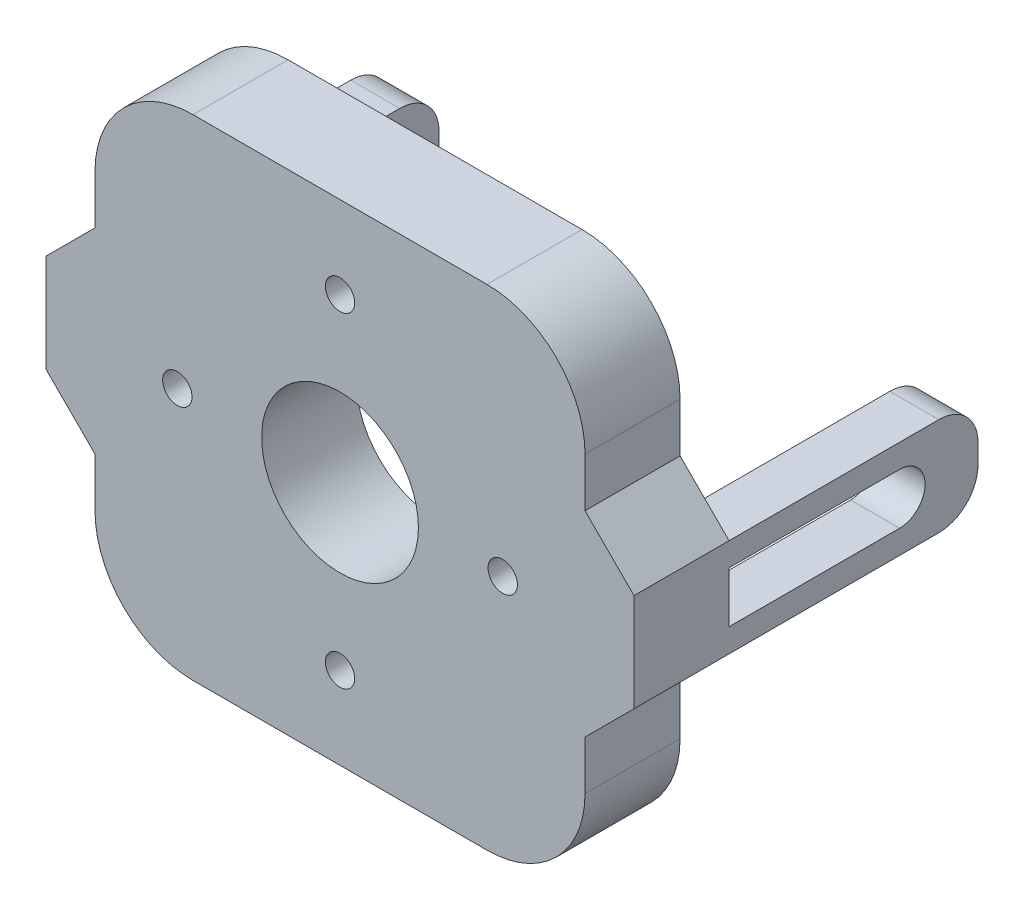
SolidWorks part; units mm, degrees
ref_plane "Front Plane" through (0, 0, 0) normal (0, 0, 1) x (1, 0, 0)
ref_plane "Top Plane" through (0, 0, 0) normal (0, 1, 0) x (1, 0, 0)
ref_plane "Right Plane" through (0, 0, 0) normal (1, 0, 0) x (0, 0, -1)
sketch "Sketch1" plane through (0, 0, 0) normal (0, 0, 1) x (1, 0, 0)
  line L0 (0, 0) -> (18.1, 0)
  line L1 (-25, -25) -> (25, -25)
  line L2 (-25, -25) -> (-25, 25)
  line L3 (-25, 25) -> (25, 25)
  line L4 (25, -25) -> (25, 25)
  line L5 (-25, -25) -> (25, 25) construction
  line L6 (-25, 25) -> (25, -25) construction
  circle A0 centre (0, 0) radius 8
  circle A1 centre (16.6, 0) radius 1.5
  circle A2 centre (0, -16.6) radius 1.5
  circle A3 centre (-16.6, 0) radius 1.5
  circle A4 centre (0, 16.6) radius 1.5
  point P19 (0, 0)
  dimension "D1" = 16
  dimension "D3" = 3
  dimension "D2" = 50
  dimension "D4" = 18.1
  dimension "D5" = 4
extrude "Boss-Extrude1" add sketch "Sketch1" along normal blind 9.7
sketch "Sketch2" plane through (0, 0, 9.7) normal (0, 0, 1) x (1, 0, 0)
  line L0 (-19.725, 0) -> (-13.475, 0)
  line L1 (-16.6, -3) -> (-16.6, 3)
  line L2 (-19.725, -1.2266) -> (-19.725, 1.2266) construction
  line L4 (-18.5752, 0) -> (-20.8748, 0) construction
  line L5 (-19.2248, 2.093) -> (-17.1002, 3.3196) construction
  line L6 (-17.5876, 1.7106) -> (-18.7374, 3.7021) construction
  line L7 (-16.0998, 3.3196) -> (-13.9752, 2.093) construction
  line L8 (-15.6124, 1.7106) -> (-14.4626, 3.7021) construction
  line L9 (-13.475, 1.2266) -> (-13.475, -1.2266) construction
  line L10 (-14.6248, 0) -> (-12.3252, 0) construction
  line L11 (-13.9752, -2.093) -> (-16.0998, -3.3196) construction
  line L12 (-15.6124, -1.7106) -> (-14.4626, -3.7021) construction
  line L13 (-17.1002, -3.3196) -> (-19.2248, -2.093) construction
  line L14 (-17.5876, -1.7106) -> (-18.7374, -3.7021) construction
  line L15 (-19.725, 0) -> (-18.1625, -2.7063)
  line L17 (-18.1625, -2.7063) -> (-15.0375, -2.7063)
  line L18 (-15.0375, -2.7063) -> (-13.475, 0)
  line L20 (-13.475, 0) -> (-15.0375, 2.7063)
  line L22 (-15.0375, 2.7063) -> (-18.1625, 2.7063)
  line L23 (-18.1625, 2.7063) -> (-19.725, 0)
  line L26 (-2.6111, 14.9422) -> (0.0953, 13.3797)
  line L27 (0.0953, 19.6297) -> (0.0953, 13.3797)
  line L28 (0.0953, 19.6297) -> (-2.6111, 18.0672)
  line L29 (-2.6111, 18.0672) -> (-2.6111, 14.9422)
  line L30 (2.8016, 14.9422) -> (2.8016, 18.0672)
  line L31 (0.0953, 13.3797) -> (2.8016, 14.9422)
  line L32 (2.8016, 18.0672) -> (0.0953, 19.6297)
  line L33 (15.0375, 2.5158) -> (13.475, -0.1905)
  line L34 (19.725, -0.1905) -> (13.475, -0.1905)
  line L35 (19.725, -0.1905) -> (18.1625, 2.5158)
  line L36 (18.1625, 2.5158) -> (15.0375, 2.5158)
  line L37 (15.0375, -2.8969) -> (18.1625, -2.8969)
  line L38 (13.475, -0.1905) -> (15.0375, -2.8969)
  line L39 (18.1625, -2.8969) -> (19.725, -0.1905)
  line L40 (2.6111, -15.1328) -> (-0.0953, -13.5703)
  line L41 (-0.0953, -19.8203) -> (-0.0953, -13.5703)
  line L42 (-0.0953, -19.8203) -> (2.6111, -18.2578)
  line L43 (2.6111, -18.2578) -> (2.6111, -15.1328)
  line L44 (-2.8016, -15.1328) -> (-2.8016, -18.2578)
  line L45 (-0.0953, -13.5703) -> (-2.8016, -15.1328)
  line L46 (-2.8016, -18.2578) -> (-0.0953, -19.8203)
  circle A2 centre (-16.6, 0) radius 1.5 construction
  circle A3 centre (-16.6, 0) radius 1.5
  circle A4 centre (-16.6, 0) radius 3.125 construction
  point P5 (-16.6, 0)
  point P8 (-16.6, 0)
  point P25 (-19.725, 0)
  point P63 (-19.725, 0)
  point P143 (0, -0.0953)
  dimension "D3" = 6.25
  dimension "D1" = 5.4127
  dimension "D4" = 6
  dimension "D5" = 4
sketch "Sketch6" plane through (0, 0, 9.7) normal (0, 0, 1) x (1, 0, 0)
  line L0 (-18.1625, -2.7063) -> (-15.0375, -2.7063) construction
  line L1 (-19.725, 0) -> (-18.1625, -2.7063) construction
  line L2 (-18.1625, 2.7063) -> (-19.725, 0) construction
  line L3 (-15.0375, 2.7063) -> (-18.1625, 2.7063) construction
  line L4 (-13.475, 0) -> (-15.0375, 2.7063) construction
  line L5 (-15.0375, -2.7063) -> (-13.475, 0) construction
  line L6 (2.6111, -18.2578) -> (2.6111, -15.1328) construction
  line L7 (-0.0953, -19.8203) -> (-0.0953, -13.5703) construction
  line L8 (-0.0953, -19.8203) -> (2.6111, -18.2578) construction
  line L9 (-2.8016, -18.2578) -> (-0.0953, -19.8203) construction
  line L10 (-2.8016, -15.1328) -> (-2.8016, -18.2578) construction
  line L11 (-0.0953, -13.5703) -> (-2.8016, -15.1328) construction
  line L12 (2.6111, -15.1328) -> (-0.0953, -13.5703) construction
  line L13 (15.0375, -2.8969) -> (18.1625, -2.8969) construction
  line L14 (19.725, -0.1905) -> (13.475, -0.1905) construction
  line L15 (18.1625, -2.8969) -> (19.725, -0.1905) construction
  line L16 (19.725, -0.1905) -> (18.1625, 2.5158) construction
  line L17 (18.1625, 2.5158) -> (15.0375, 2.5158) construction
  line L18 (15.0375, 2.5158) -> (13.475, -0.1905) construction
  line L19 (13.475, -0.1905) -> (15.0375, -2.8969) construction
  line L20 (0.0953, 19.6297) -> (-2.6111, 18.0672) construction
  line L21 (-2.6111, 18.0672) -> (-2.6111, 14.9422) construction
  line L22 (2.8016, 18.0672) -> (0.0953, 19.6297) construction
  line L23 (0.0953, 19.6297) -> (0.0953, 13.3797) construction
  line L24 (2.8016, 14.9422) -> (2.8016, 18.0672) construction
  line L25 (0.0953, 13.3797) -> (2.8016, 14.9422) construction
  line L26 (-2.6111, 14.9422) -> (0.0953, 13.3797) construction
  line L27 (-18.1625, -2.7063) -> (-15.0375, -2.7063)
  line L28 (-19.725, 0) -> (-18.1625, -2.7063)
  line L29 (-18.1625, 2.7063) -> (-19.725, 0)
  line L30 (-15.0375, 2.7063) -> (-18.1625, 2.7063)
  line L31 (-13.475, 0) -> (-15.0375, 2.7063)
  line L32 (-15.0375, -2.7063) -> (-13.475, 0)
  line L33 (2.6111, -18.2578) -> (2.6111, -15.1328)
  line L34 (-0.0953, -19.8203) -> (-0.0953, -13.5703)
  line L35 (-0.0953, -19.8203) -> (2.6111, -18.2578)
  line L36 (-2.8016, -18.2578) -> (-0.0953, -19.8203)
  line L37 (-2.8016, -15.1328) -> (-2.8016, -18.2578)
  line L38 (-0.0953, -13.5703) -> (-2.8016, -15.1328)
  line L39 (2.6111, -15.1328) -> (-0.0953, -13.5703)
  line L40 (15.0375, -2.8969) -> (18.1625, -2.8969)
  line L41 (19.725, -0.1905) -> (13.475, -0.1905)
  line L42 (18.1625, -2.8969) -> (19.725, -0.1905)
  line L43 (19.725, -0.1905) -> (18.1625, 2.5158)
  line L44 (18.1625, 2.5158) -> (15.0375, 2.5158)
  line L45 (15.0375, 2.5158) -> (13.475, -0.1905)
  line L46 (13.475, -0.1905) -> (15.0375, -2.8969)
  line L47 (0.0953, 19.6297) -> (-2.6111, 18.0672)
  line L48 (-2.6111, 18.0672) -> (-2.6111, 14.9422)
  line L49 (2.8016, 18.0672) -> (0.0953, 19.6297)
  line L50 (0.0953, 19.6297) -> (0.0953, 13.3797)
  line L51 (2.8016, 14.9422) -> (2.8016, 18.0672)
  line L52 (0.0953, 13.3797) -> (2.8016, 14.9422)
  line L53 (-2.6111, 14.9422) -> (0.0953, 13.3797)
  circle A0 centre (16.6, 0) radius 1.5 construction
  circle A1 centre (0, -16.6) radius 1.5 construction
  circle A2 centre (0, 16.6) radius 1.5 construction
  circle A3 centre (-16.6, 0) radius 1.5 construction
  circle A4 centre (16.6, 0) radius 1.5
  circle A5 centre (0, -16.6) radius 1.5
  circle A6 centre (0, 16.6) radius 1.5
  circle A7 centre (-16.6, 0) radius 1.5
  point P0 (-2.6111, 18.0672)
fillet "Fillet2" radius 10 4 edges at (-25, -25, 4.85) (25, -25, 4.85) (25, 25, 4.85) (-25, 25, 4.85)
sketch "Sketch7" plane through (25, 0, 0) normal (1, 0, 0) x (0, 0, -1)
  line L1 (-9.7, 5) -> (25.4, 5)
  line L2 (-9.7, 5) -> (-9.7, -5)
  line L3 (-9.7, -5) -> (25.4, -5)
  line L4 (25.4, 5) -> (25.4, -5)
  line L5 (0, 0) -> (20, 0) construction
  line L6 (0, -15) -> (0, 15) construction
  line L7 (17.4, 2.6) -> (0, 2.6)
  line L8 (0, 2.6) -> (0, -2.6)
  line L9 (0, -2.6) -> (17.4, -2.6)
  line L10 (-9.7, -15) -> (-9.7, 15) construction
  circle A0 centre (17.4, 0) radius 2.6
  dimension "D1" = 5.2
  dimension "D5" = 8
  dimension "D2" = 5
  dimension "D3" = 5
  dimension "D4" = 20
extrude "Boss-Extrude3" add sketch "Sketch7" along normal blind 5
pattern_circular "CirPattern6" count 2 every 180 about axis through (0, 0, 0) along (0, 0, 1) of "Boss-Extrude3"
sketch "Sketch9" plane through (0, 0, 0) normal (0, 0, -1) x (-1, 0, 0)
  line L0 (2.8016, -15.1328) -> (2.8016, -18.2578) construction
  line L1 (0.0953, -13.5703) -> (2.8016, -15.1328) construction
  line L2 (-2.6111, -15.1328) -> (0.0953, -13.5703) construction
  line L3 (-2.6111, -18.2578) -> (-2.6111, -15.1328) construction
  line L4 (0.0953, -19.8203) -> (-2.6111, -18.2578) construction
  line L5 (2.8016, -18.2578) -> (0.0953, -19.8203) construction
  line L6 (18.1625, -2.7063) -> (15.0375, -2.7063) construction
  line L7 (19.725, 0) -> (18.1625, -2.7063) construction
  line L8 (18.1625, 2.7063) -> (19.725, 0) construction
  line L9 (15.0375, 2.7063) -> (18.1625, 2.7063) construction
  line L10 (13.475, 0) -> (15.0375, 2.7063) construction
  line L11 (15.0375, -2.7063) -> (13.475, 0) construction
  line L12 (2.6111, 14.9422) -> (-0.0953, 13.3797) construction
  line L13 (2.6111, 18.0672) -> (2.6111, 14.9422) construction
  line L14 (-0.0953, 19.6297) -> (2.6111, 18.0672) construction
  line L15 (-2.8016, 18.0672) -> (-0.0953, 19.6297) construction
  line L16 (-2.8016, 14.9422) -> (-2.8016, 18.0672) construction
  line L17 (-0.0953, 13.3797) -> (-2.8016, 14.9422) construction
  line L18 (-13.475, -0.1905) -> (-15.0375, -2.8969) construction
  line L19 (-15.0375, 2.5158) -> (-13.475, -0.1905) construction
  line L20 (-18.1625, 2.5158) -> (-15.0375, 2.5158) construction
  line L21 (-19.725, -0.1905) -> (-18.1625, 2.5158) construction
  line L22 (-18.1625, -2.8969) -> (-19.725, -0.1905) construction
  line L23 (-15.0375, -2.8969) -> (-18.1625, -2.8969) construction
  line L24 (2.8016, -15.1328) -> (2.8016, -18.2578)
  line L25 (0.0953, -13.5703) -> (2.8016, -15.1328)
  line L26 (-2.6111, -15.1328) -> (0.0953, -13.5703)
  line L27 (-2.6111, -18.2578) -> (-2.6111, -15.1328)
  line L28 (0.0953, -19.8203) -> (-2.6111, -18.2578)
  line L29 (2.8016, -18.2578) -> (0.0953, -19.8203)
  line L30 (18.1625, -2.7063) -> (15.0375, -2.7063)
  line L31 (19.725, 0) -> (18.1625, -2.7063)
  line L32 (18.1625, 2.7063) -> (19.725, 0)
  line L33 (15.0375, 2.7063) -> (18.1625, 2.7063)
  line L34 (13.475, 0) -> (15.0375, 2.7063)
  line L35 (15.0375, -2.7063) -> (13.475, 0)
  line L36 (2.6111, 14.9422) -> (-0.0953, 13.3797)
  line L37 (2.6111, 18.0672) -> (2.6111, 14.9422)
  line L38 (-0.0953, 19.6297) -> (2.6111, 18.0672)
  line L39 (-2.8016, 18.0672) -> (-0.0953, 19.6297)
  line L40 (-2.8016, 14.9422) -> (-2.8016, 18.0672)
  line L41 (-0.0953, 13.3797) -> (-2.8016, 14.9422)
  line L42 (-13.475, -0.1905) -> (-15.0375, -2.8969)
  line L43 (-15.0375, 2.5158) -> (-13.475, -0.1905)
  line L44 (-18.1625, 2.5158) -> (-15.0375, 2.5158)
  line L45 (-19.725, -0.1905) -> (-18.1625, 2.5158)
  line L46 (-18.1625, -2.8969) -> (-19.725, -0.1905)
  line L47 (-15.0375, -2.8969) -> (-18.1625, -2.8969)
extrude "Cut-Extrude1" cut sketch "Sketch9" against normal blind 2.5
fillet "Fillet3" radius 4 4 edges at (27.5, -5, -25.4) (27.5, 5, -25.4) (-27.5, -5, -25.4) (-27.5, 5, -25.4)
chamfer "Chamfer2" distance 5 angle 45 4 edges at (-25, 5, 4.85) (-25, -5, 4.85) (25, -5, 4.85) (25, 5, 4.85)
